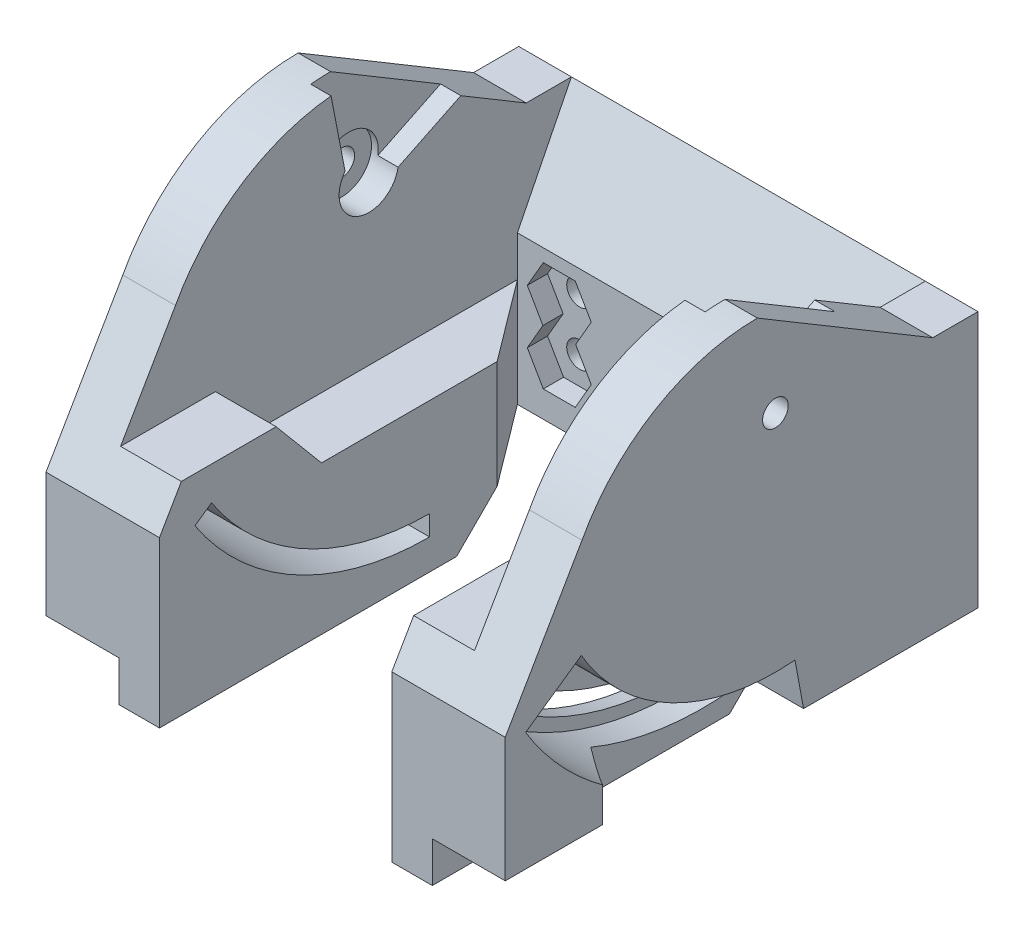
SolidWorks part; units mm, degrees
ref_plane "Alzado" through (0, 0, 0) normal (0, 0, 1) x (1, 0, 0)
ref_plane "Planta" through (0, 0, 0) normal (0, 1, 0) x (1, 0, 0)
ref_plane "Vista lateral" through (0, 0, 0) normal (1, 0, 0) x (0, 0, -1)
sketch "Croquis1" plane through (0, 0, 0) normal (0, 0, 1) x (1, 0, 0)
  line L1 (-48.8873, 14.6225) -> (-14.8873, 14.6225)
  line L2 (-48.8873, 14.6225) -> (-48.8873, -4.3775)
  line L3 (-48.8873, -4.3775) -> (-14.8873, -4.3775)
  line L4 (-14.8873, 14.6225) -> (-14.8873, -4.3775)
  dimension "D1" = 19
  dimension "D2" = 34
extrude "Saliente-Extruir1" add sketch "Croquis1" along normal blind 35
sketch "Croquis2" plane through (0, -4.3775, 0) normal (0, -1, 0) x (1, 0, 0)
  line L0 (-48.8873, 35) -> (-14.8873, 35) construction
  line L1 (-44.9873, 35) -> (-18.7873, 35)
  line L2 (-44.9873, 35) -> (-44.9873, 4)
  line L3 (-44.9873, 4) -> (-18.7873, 4)
  line L4 (-18.7873, 35) -> (-18.7873, 4)
  line L5 (-48.8873, 35) -> (-48.8873, 0) construction
  line L6 (-14.8873, 35) -> (-14.8873, 0) construction
  line L7 (-48.8873, 0) -> (-14.8873, 0) construction
  dimension "D1" = 3.9
  dimension "D2" = 3.9
  dimension "D3" = 26.2
  dimension "D4" = 4
extrude "Cortar-Extruir1" cut sketch "Croquis2" against normal blind 25
sketch "Croquis4" plane through (-18.7873, 0, 0) normal (-1, 0, 0) x (0, 0, 1)
  line L0 (4, 14.6225) -> (4, 6.6225)
  line L1 (4, 14.6225) -> (4, -4.3775) construction
  line L2 (4, 6.6225) -> (0, 14.6225)
  line L3 (0, 14.6225) -> (4, 14.6225)
extrude "Cortar-Extruir3" cut sketch "Croquis4" along normal up to vertex (26.2 mm away) up to point (-44.9873, 14.6225, 4)
sketch "Croquis9" plane through (-14.8873, 0, 0) normal (1, 0, 0) x (0, 0, -1)
  line L0 (-35, 14.6225) -> (0, 14.6225) construction
  line L1 (-29.3158, 14.6225) -> (-3.3495, 14.6225)
  line L7 (-35, -4.3775) -> (0, -4.3775) construction
  arc A0 (-29.3158, 14.6225) -> (-3.3495, 14.6225) centre (-16.3327, 7.6225) cw
  dimension "D2" = 12
extrude "Saliente-Extruir2" add sketch "Croquis9" against normal up to vertex (34 mm away) up to point (-48.8873, 14.6225, 35)
sketch "Croquis10" plane through (0, 14.6225, 0) normal (0, -1, 0) x (1, 0, 0)
  line L1 (-44.9873, 29.3158) -> (-18.7873, 29.3158)
  line L2 (-44.9873, 29.3158) -> (-44.9873, 3.3495)
  line L3 (-44.9873, 3.3495) -> (-18.7873, 3.3495)
  line L4 (-18.7873, 29.3158) -> (-18.7873, 3.3495)
extrude "Cortar-Extruir4" cut sketch "Croquis10" against normal blind 10
sketch "Croquis18" plane through (0, 0, 0) normal (0, 0, -1) x (-1, 0, 0)
  line L0 (48.8873, -4.3775) -> (14.8873, -4.3775) construction
  line L2 (48.8873, 14.6225) -> (48.8873, -4.3775) construction
  circle A0 centre (41.8873, -0.3775) radius 0.95
  circle A1 centre (21.8873, -0.3775) radius 0.95
  circle A2 centre (21.8873, 3.6225) radius 0.95
  circle A3 centre (41.8873, 3.6225) radius 0.95
  dimension "D1" = 4
  dimension "D2" = 7
  dimension "D5" = 4
  dimension "D3" = 2
  dimension "D4" = 2
extrude "Cortar-Extruir11" cut sketch "Croquis18" against normal up to vertex (4 mm away) up to point (-18.7873, -4.3775, 4)
sketch "Croquis19" plane through (0, 0, 4) normal (0, 0, 1) x (1, 0, 0)
  line L0 (-39.5201, -0.3775) -> (-40.6748, 1.6225)
  line L1 (-19.5201, -0.3775) -> (-20.6748, 1.6225)
  line L3 (-23.0997, 1.6225) -> (-24.2544, -0.3775)
  line L4 (-24.2544, -0.3775) -> (-23.0708, -2.4275)
  line L5 (-23.0708, -2.4275) -> (-20.7037, -2.4275)
  line L6 (-20.7037, -2.4275) -> (-19.5201, -0.3775)
  line L8 (-43.0997, 1.6225) -> (-44.2544, -0.3775)
  line L9 (-44.2544, -0.3775) -> (-43.0708, -2.4275)
  line L10 (-43.0708, -2.4275) -> (-40.7037, -2.4275)
  line L11 (-40.7037, -2.4275) -> (-39.5201, -0.3775)
  line L12 (-39.5201, 3.6225) -> (-40.7037, 5.6725)
  line L13 (-40.7037, 5.6725) -> (-43.0708, 5.6725)
  line L14 (-43.0708, 5.6725) -> (-44.2544, 3.6225)
  line L15 (-44.2544, 3.6225) -> (-43.0997, 1.6225)
  line L17 (-40.6748, 1.6225) -> (-39.5201, 3.6225)
  line L18 (-19.5201, 3.6225) -> (-20.7037, 5.6725)
  line L19 (-20.7037, 5.6725) -> (-23.0708, 5.6725)
  line L20 (-23.0708, 5.6725) -> (-24.2544, 3.6225)
  line L21 (-24.2544, 3.6225) -> (-23.0997, 1.6225)
  line L23 (-20.6748, 1.6225) -> (-19.5201, 3.6225)
  line L29 (-43.0708, 1.5725) -> (-40.7037, 1.5725) [skipped]
  line L30 (-23.0708, 1.5725) -> (-20.7037, 1.5725) [skipped]
  line L31 (-20.7037, 1.6725) -> (-23.0708, 1.6725) [skipped]
  circle A0 centre (-21.8873, -0.3775) radius 2.05 construction
  circle A1 centre (-41.8873, -0.3775) radius 2.05 construction
  circle A2 centre (-41.8873, 3.6225) radius 2.05 construction
  circle A3 centre (-21.8873, 3.6225) radius 2.05 construction
  dimension "D1" = 4.1
  dimension "D2" = 2
  dimension "D3" = 2
extrude "Cortar-Extruir12" cut sketch "Croquis19" against normal blind 1.5
sketch "Croquis21" plane through (-14.8873, 0, 0) normal (1, 0, 0) x (0, 0, -1)
  line L0 (0, -4.3775) -> (0, 14.6225) construction
  line L2 (-35, -4.3775) -> (0, -4.3775) construction
  circle A0 centre (-15, 15.6225) radius 0.95
  dimension "D1" = 15
  dimension "D2" = 20
extrude "Cortar-Extruir14" cut sketch "Croquis21" against normal up to vertex (34 mm away) up to point (-48.8873, 14.6225, 3.3495)
sketch "Croquis23" plane through (0, -4.3775, 0) normal (0, -1, 0) x (1, 0, 0)
  line L0 (-44.9873, 35) -> (-40.4873, 35)
  line L1 (-40.4873, 35) -> (-40.4873, 10)
  line L2 (-40.4873, 10) -> (-44.9873, 4)
  line L3 (-44.9873, 35) -> (-44.9873, 4) construction
  line L4 (-44.9873, 4) -> (-44.9873, 35)
  line L5 (-18.7873, 35) -> (-23.2873, 35)
  line L6 (-23.2873, 35) -> (-23.2873, 10)
  line L7 (-23.2873, 10) -> (-18.7873, 4)
  line L8 (-18.7873, 4) -> (-18.7873, 35)
  dimension "D1" = 25
  dimension "D2" = 25
extrude "Saliente-Extruir3" add sketch "Croquis23" against normal blind 8
sketch "Croquis25" plane through (0, -4.3775, 0) normal (0, -1, 0) x (1, 0, 0)
  line L0 (-40.4873, 35) -> (-43.4873, 35)
  line L1 (-20.2873, 35) -> (-23.2873, 35)
  line L2 (-43.4873, 35) -> (-43.4873, 10)
  line L3 (-43.4873, 10) -> (-40.4873, 10)
  line L4 (-40.4873, 35) -> (-40.4873, 10)
  line L10 (-20.2873, 35) -> (-20.2873, 10)
  line L11 (-20.2873, 10) -> (-23.2873, 10)
  line L12 (-23.2873, 35) -> (-23.2873, 10)
  dimension "D1" = 3
  dimension "D2" = 3
extrude "Saliente-Extruir4" add sketch "Croquis25" along normal blind 3
sketch "Croquis43" plane through (0, 3.6225, 0) normal (0, 1, 0) x (1, 0, 0)
  line L0 (-23.2873, -35) -> (-23.2873, -10) construction
  line L1 (-18.7873, -35) -> (-23.2873, -35)
  line L2 (-18.7873, -35) -> (-18.7873, -23)
  line L3 (-18.7873, -23) -> (-23.2873, -23)
  line L4 (-23.2873, -35) -> (-23.2873, -23)
  line L5 (-44.9873, -35) -> (-44.9873, -4) construction
  line L6 (-40.4873, -35) -> (-44.9873, -35)
  line L7 (-40.4873, -35) -> (-40.4873, -23)
  line L8 (-40.4873, -23) -> (-44.9873, -23)
  line L9 (-44.9873, -35) -> (-44.9873, -23)
  dimension "D1" = 12
  dimension "D2" = 12
extrude "Saliente-Extruir8" add sketch "Croquis43" along normal blind 4
sketch "Croquis27" plane through (-14.8873, 0, 0) normal (1, 0, 0) x (0, 0, -1)
  line L0 (-13.5494, -0.9426) -> (-12.6355, -5.8873)
  line L1 (-33.492, 4.3837) -> (-29.3712, 7.2574)
  arc A2 (-29.3712, 7.2574) -> (-13.5494, -0.9426) centre (-15, 15.6225) ccw
  arc A3 (-33.492, 4.3837) -> (-12.6355, -5.8873) centre (-15, 15.6225) ccw
  dimension "D2" = 21.6395
extrude "Cortar-Extruir18" cut sketch "Croquis27" against normal blind 7.4
sketch "Croquis24" plane through (-14.8873, 0, 0) normal (1, 0, 0) x (0, 0, -1)
  line L0 (-15, -3.6275) -> (-15, -5.1273)
  line L1 (-31.1427, 5.1356) -> (-32.3723, 4.2754)
  arc A2 (-31.1427, 5.1356) -> (-15, -3.6275) centre (-15, 15.6225) ccw
  arc A3 (-32.3723, 4.2754) -> (-15, -5.1273) centre (-15, 15.6225) ccw
  dimension "D1" = 19.25
  dimension "D2" = 20.7498
extrude "Cortar-Extruir16" cut sketch "Croquis24" against normal up to vertex (34 mm away) up to point (-48.8873, -4.3775, 35)
sketch "Croquis29" plane through (-18.7873, 0, 0) normal (-1, 0, 0) x (0, 0, 1)
  line L0 (17.7974, 22.2996) -> (16.5, 15.6225)
  line L1 (6.2969, 18.4321) -> (13.7431, 14.804)
  arc A0 (6.2969, 18.4321) -> (17.7974, 22.2996) centre (16.3327, 7.6225) cw
  arc A1 (29.3158, 14.6225) -> (3.3495, 14.6225) centre (16.3327, 7.6225) ccw construction
  arc A2 (16.5, 15.6225) -> (13.7431, 14.804) centre (15, 15.6225) cw
extrude "Cortar-Extruir20" cut sketch "Croquis29" against normal blind 1.5
extrude "Cortar-Extruir21" cut sketch "Croquis29<2>" along normal blind 27.7
sketch "Croquis29<2>" plane through (-18.7873, 0, 0) normal (-1, 0, 0) x (0, 0, 1) same geometry as "Croquis29"
sketch "Croquis30" plane through (-48.8873, 0, 0) normal (-1, 0, 0) x (0, 0, 1)
  line L0 (29.3158, 14.6225) -> (35, 4.8278)
  line L1 (35, 14.6225) -> (35, -4.3775) construction
  line L2 (35, 4.8278) -> (35, 14.6225)
  line L3 (35, 14.6225) -> (29.3158, 14.6225)
extrude "Cortar-Extruir22" cut sketch "Croquis30" against normal up to vertex (34 mm away) up to point (-14.8873, 14.6225, 35)
sketch "Croquis35" plane through (0, -4.3775, 0) normal (0, -1, 0) x (1, 0, 0)
  line L0 (-20.2873, 23.2623) -> (-14.8873, 23.2623)
  line L2 (-20.2873, 23.2623) -> (-14.8873, 23.2623) construction
  line L4 (-14.8873, 23.2623) -> (-14.8873, 27.7963)
  line L5 (-14.8873, 35) -> (-14.8873, 23.2623) construction
  line L6 (-14.8873, 27.7963) -> (-20.2873, 23.2623)
extrude "Cortar-Extruir23" cut sketch "Croquis35" against normal blind 3
sketch "Croquis36" plane through (-18.7873, 0, 0) normal (-1, 0, 0) x (0, 0, 1)
  circle A0 centre (15, 15.6225) radius 2.2
extrude "Cortar-Extruir24" cut sketch "Croquis36" against normal blind 2
extrude "Cortar-Extruir25" cut sketch "Croquis36<2>" along normal blind 28.2
sketch "Croquis36<2>" plane through (-18.7873, 0, 0) normal (-1, 0, 0) x (0, 0, 1) same geometry as "Croquis36"
sketch "Croquis38" plane through (-48.8873, 0, 0) normal (-1, 0, 0) x (0, 0, 1)
  line L0 (3.3495, 14.6225) -> (16.3327, 22.3725)
  line L1 (16.3327, 22.3725) -> (3.3495, 22.3725)
  line L2 (3.3495, 22.3725) -> (3.3495, 14.6225)
  arc A0 (29.3158, 14.6225) -> (3.3495, 14.6225) centre (16.3327, 7.6225) ccw construction
extrude "Cortar-Extruir26" cut sketch "Croquis38" against normal up to vertex (34 mm away) up to point (-14.8873, 14.6225, 3.3495)
sketch "Croquis40" plane through (-48.8873, 0, 0) normal (-1, 0, 0) x (0, 0, 1)
  line L0 (24.4625, 4.9679) -> (27.805, 0.9845)
  line L1 (27.805, 0.9845) -> (27.1921, 0.4702)
  line L2 (27.1921, 0.4702) -> (23.8496, 4.4537)
  line L3 (23.5, 4.1807) -> (26.4826, -0.0789)
  line L4 (26.4826, -0.0789) -> (25.8272, -0.5377)
  line L5 (25.8272, -0.5377) -> (22.8446, 3.7219)
  line L6 (22.4696, 3.4848) -> (25.0696, -1.0186)
  line L7 (24.4625, 4.9679) -> (23.8496, 4.4537)
  line L8 (25.0696, -1.0186) -> (24.3768, -1.4186)
  line L9 (24.3768, -1.4186) -> (21.7768, 3.0848)
  line L10 (22.8446, 3.7219) -> (23.5, 4.1807)
  line L11 (21.3819, 2.8831) -> (23.5795, -1.8297)
  line L12 (23.5795, -1.8297) -> (22.8544, -2.1678)
  line L13 (22.4696, 3.4848) -> (21.7768, 3.0848)
  line L14 (22.8544, -2.1678) -> (20.6568, 2.545)
  line L16 (21.3819, 2.8831) -> (20.6568, 2.545)
  circle A1 centre (15, 15.6225) radius 0.95 construction
  dimension "D2" = 14.2443
  dimension "D3" = 14.248
  dimension "D4" = 14.2464
  dimension "D5" = 0.8
  dimension "D6" = 14.2429
  dimension "D8" = 0.8
  dimension "D9" = 0.8
  dimension "D11" = 0.8
extrude "Cortar-Extruir27" cut sketch "Croquis40" against normal blind 1
sketch "Croquis41" plane through (-20.2873, 0, 0) normal (1, 0, 0) x (0, 0, -1)
  line L0 (-10, -4.3775) -> (-10, -7.3775)
  line L1 (-10, -7.3775) -> (-10, -4.3775) construction
  line L2 (-10, -7.3775) -> (-13, -7.3775)
  line L3 (-10, -7.3775) -> (-35, -7.3775) construction
  line L4 (-13, -7.3775) -> (-10, -4.3775)
extrude "Cortar-Extruir28" cut sketch "Croquis41" against normal up to vertex (23.2 mm away) up to point (-43.4873, -7.3775, 10)
sketch "Croquis44" plane through (-18.7873, 0, 0) normal (-1, 0, 0) x (0, 0, 1)
  line L0 (23, 7.6225) -> (26.3626, 7.6225)
  line L1 (33.3781, 7.6225) -> (23, 7.6225) construction
  line L2 (26.3626, 7.6225) -> (23, 3.6225)
  line L3 (23, 3.6225) -> (23, 7.6225)
extrude "Cortar-Extruir29" cut sketch "Croquis44" along normal up to vertex (26.2 mm away) up to point (-44.9873, 7.6225, 23)
